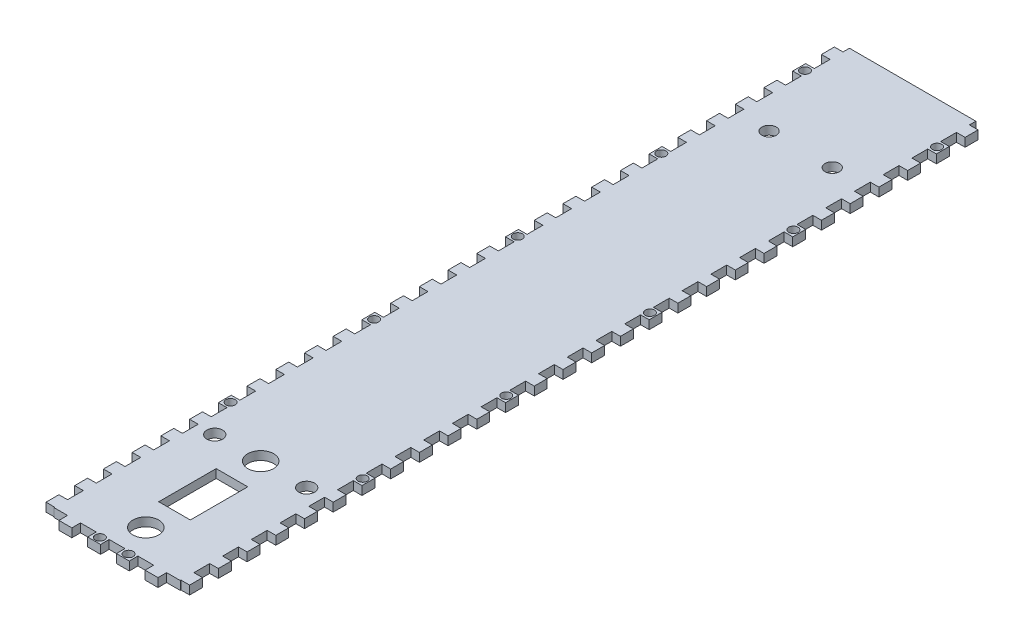
SolidWorks part; units mm, degrees
ref_plane "Plan de face" through (0, 0, 0) normal (0, 0, 1) x (1, 0, 0)
ref_plane "Plan de dessus" through (0, 0, 0) normal (0, 1, 0) x (1, 0, 0)
ref_plane "Plan de droite" through (0, 0, 0) normal (1, 0, 0) x (0, 0, -1)
sketch "Sketch1" plane through (0, 0, 0) normal (0, 0, 1) x (1, 0, 0)
  line L1 (-30.0201, 10.5217) -> (13.9799, 10.5217)
  line L2 (-30.0201, 10.5217) -> (-30.0201, 7.5217)
  line L3 (-30.0201, 7.5217) -> (13.9799, 7.5217)
  line L4 (13.9799, 10.5217) -> (13.9799, 7.5217)
  dimension "D1" = 44
  dimension "D2" = 3
extrude "Boss-Extrude1" add sketch "Sketch1" along normal blind 277
sketch "Sketch4" plane through (13.9799, 0, 0) normal (1, 0, 0) x (0, 0, -1)
  line L0 (-277, 10.5217) -> (0, 10.5217) construction
  line L1 (-276.75, 10.5217) -> (-272.25, 10.5217)
  line L2 (-276.75, 10.5217) -> (-276.75, 7.5217)
  line L3 (-276.75, 7.5217) -> (-272.25, 7.5217)
  line L4 (-272.25, 10.5217) -> (-272.25, 7.5217)
  line L5 (-277, 7.5217) -> (0, 7.5217) construction
  line L6 (-277, 7.5217) -> (-277, 10.5217) construction
  line L7 (-266.75, 10.5217) -> (-266.75, 7.5217)
  line L8 (-266.75, 10.5217) -> (-262.25, 10.5217)
  line L9 (-262.25, 10.5217) -> (-262.25, 7.5217)
  line L10 (-266.75, 7.5217) -> (-262.25, 7.5217)
  line L11 (-256.75, 10.5217) -> (-256.75, 7.5217)
  line L12 (-256.75, 10.5217) -> (-252.25, 10.5217)
  line L13 (-252.25, 10.5217) -> (-252.25, 7.5217)
  line L14 (-256.75, 7.5217) -> (-252.25, 7.5217)
  line L15 (-246.75, 10.5217) -> (-246.75, 7.5217)
  line L16 (-246.75, 10.5217) -> (-242.25, 10.5217)
  line L17 (-242.25, 10.5217) -> (-242.25, 7.5217)
  line L18 (-246.75, 7.5217) -> (-242.25, 7.5217)
  line L19 (-236.75, 10.5217) -> (-236.75, 7.5217)
  line L20 (-236.75, 10.5217) -> (-232.25, 10.5217)
  line L21 (-232.25, 10.5217) -> (-232.25, 7.5217)
  line L22 (-236.75, 7.5217) -> (-232.25, 7.5217)
  line L23 (-226.75, 10.5217) -> (-226.75, 7.5217)
  line L24 (-226.75, 10.5217) -> (-222.25, 10.5217)
  line L25 (-222.25, 10.5217) -> (-222.25, 7.5217)
  line L26 (-226.75, 7.5217) -> (-222.25, 7.5217)
  line L27 (-216.75, 10.5217) -> (-216.75, 7.5217)
  line L28 (-216.75, 10.5217) -> (-212.25, 10.5217)
  line L29 (-212.25, 10.5217) -> (-212.25, 7.5217)
  line L30 (-216.75, 7.5217) -> (-212.25, 7.5217)
  line L31 (-206.75, 10.5217) -> (-206.75, 7.5217)
  line L32 (-206.75, 10.5217) -> (-202.25, 10.5217)
  line L33 (-202.25, 10.5217) -> (-202.25, 7.5217)
  line L34 (-206.75, 7.5217) -> (-202.25, 7.5217)
  line L35 (-196.75, 10.5217) -> (-196.75, 7.5217)
  line L36 (-196.75, 10.5217) -> (-192.25, 10.5217)
  line L37 (-192.25, 10.5217) -> (-192.25, 7.5217)
  line L38 (-196.75, 7.5217) -> (-192.25, 7.5217)
  line L39 (-186.75, 10.5217) -> (-186.75, 7.5217)
  line L40 (-186.75, 10.5217) -> (-182.25, 10.5217)
  line L41 (-182.25, 10.5217) -> (-182.25, 7.5217)
  line L42 (-186.75, 7.5217) -> (-182.25, 7.5217)
  line L43 (-176.75, 10.5217) -> (-176.75, 7.5217)
  line L44 (-176.75, 10.5217) -> (-172.25, 10.5217)
  line L45 (-172.25, 10.5217) -> (-172.25, 7.5217)
  line L46 (-176.75, 7.5217) -> (-172.25, 7.5217)
  line L47 (-166.75, 10.5217) -> (-166.75, 7.5217)
  line L48 (-166.75, 10.5217) -> (-162.25, 10.5217)
  line L49 (-162.25, 10.5217) -> (-162.25, 7.5217)
  line L50 (-166.75, 7.5217) -> (-162.25, 7.5217)
  line L51 (-156.75, 10.5217) -> (-156.75, 7.5217)
  line L52 (-156.75, 10.5217) -> (-152.25, 10.5217)
  line L53 (-152.25, 10.5217) -> (-152.25, 7.5217)
  line L54 (-156.75, 7.5217) -> (-152.25, 7.5217)
  line L55 (-146.75, 10.5217) -> (-146.75, 7.5217)
  line L56 (-146.75, 10.5217) -> (-142.25, 10.5217)
  line L57 (-142.25, 10.5217) -> (-142.25, 7.5217)
  line L58 (-146.75, 7.5217) -> (-142.25, 7.5217)
  line L59 (-136.75, 10.5217) -> (-136.75, 7.5217)
  line L60 (-136.75, 10.5217) -> (-132.25, 10.5217)
  line L61 (-132.25, 10.5217) -> (-132.25, 7.5217)
  line L62 (-136.75, 7.5217) -> (-132.25, 7.5217)
  line L63 (-126.75, 10.5217) -> (-126.75, 7.5217)
  line L64 (-126.75, 10.5217) -> (-122.25, 10.5217)
  line L65 (-122.25, 10.5217) -> (-122.25, 7.5217)
  line L66 (-126.75, 7.5217) -> (-122.25, 7.5217)
  line L67 (-116.75, 10.5217) -> (-116.75, 7.5217)
  line L68 (-116.75, 10.5217) -> (-112.25, 10.5217)
  line L69 (-112.25, 10.5217) -> (-112.25, 7.5217)
  line L70 (-116.75, 7.5217) -> (-112.25, 7.5217)
  line L71 (-106.75, 10.5217) -> (-106.75, 7.5217)
  line L72 (-106.75, 10.5217) -> (-102.25, 10.5217)
  line L73 (-102.25, 10.5217) -> (-102.25, 7.5217)
  line L74 (-106.75, 7.5217) -> (-102.25, 7.5217)
  line L75 (-96.75, 10.5217) -> (-96.75, 7.5217)
  line L76 (-96.75, 10.5217) -> (-92.25, 10.5217)
  line L77 (-92.25, 10.5217) -> (-92.25, 7.5217)
  line L78 (-96.75, 7.5217) -> (-92.25, 7.5217)
  line L79 (-86.75, 10.5217) -> (-86.75, 7.5217)
  line L80 (-86.75, 10.5217) -> (-82.25, 10.5217)
  line L81 (-82.25, 10.5217) -> (-82.25, 7.5217)
  line L82 (-86.75, 7.5217) -> (-82.25, 7.5217)
  line L83 (-76.75, 10.5217) -> (-76.75, 7.5217)
  line L84 (-76.75, 10.5217) -> (-72.25, 10.5217)
  line L85 (-72.25, 10.5217) -> (-72.25, 7.5217)
  line L86 (-76.75, 7.5217) -> (-72.25, 7.5217)
  line L87 (-66.75, 10.5217) -> (-66.75, 7.5217)
  line L88 (-66.75, 10.5217) -> (-62.25, 10.5217)
  line L89 (-62.25, 10.5217) -> (-62.25, 7.5217)
  line L90 (-66.75, 7.5217) -> (-62.25, 7.5217)
  line L91 (-56.75, 10.5217) -> (-56.75, 7.5217)
  line L92 (-56.75, 10.5217) -> (-52.25, 10.5217)
  line L93 (-52.25, 10.5217) -> (-52.25, 7.5217)
  line L94 (-56.75, 7.5217) -> (-52.25, 7.5217)
  line L95 (-46.75, 10.5217) -> (-46.75, 7.5217)
  line L96 (-46.75, 10.5217) -> (-42.25, 10.5217)
  line L97 (-42.25, 10.5217) -> (-42.25, 7.5217)
  line L98 (-46.75, 7.5217) -> (-42.25, 7.5217)
  line L99 (-36.75, 10.5217) -> (-36.75, 7.5217)
  line L100 (-36.75, 10.5217) -> (-32.25, 10.5217)
  line L101 (-32.25, 10.5217) -> (-32.25, 7.5217)
  line L102 (-36.75, 7.5217) -> (-32.25, 7.5217)
  line L103 (-26.75, 10.5217) -> (-26.75, 7.5217)
  line L104 (-26.75, 10.5217) -> (-22.25, 10.5217)
  line L105 (-22.25, 10.5217) -> (-22.25, 7.5217)
  line L106 (-26.75, 7.5217) -> (-22.25, 7.5217)
  line L107 (-16.75, 10.5217) -> (-16.75, 7.5217)
  line L108 (-16.75, 10.5217) -> (-12.25, 10.5217)
  line L109 (-12.25, 10.5217) -> (-12.25, 7.5217)
  line L110 (-16.75, 7.5217) -> (-12.25, 7.5217)
  line L111 (-6.75, 10.5217) -> (-6.75, 7.5217)
  line L112 (-6.75, 10.5217) -> (-2.25, 10.5217)
  line L113 (-2.25, 10.5217) -> (-2.25, 7.5217)
  line L114 (-6.75, 7.5217) -> (-2.25, 7.5217)
  dimension "D1" = 0.25
  dimension "D2" = 4.5
  dimension "D3" = 28
extrude "Boss-Extrude2" add sketch "Sketch4" along normal blind 3
sketch "Sketch5" plane through (-30.0201, 0, 0) normal (-1, 0, 0) x (0, 0, 1)
  line L0 (277, 7.5217) -> (0, 7.5217) construction
  line L1 (276.75, 7.5217) -> (272.25, 7.5217)
  line L2 (276.75, 7.5217) -> (276.75, 10.5217)
  line L3 (276.75, 10.5217) -> (272.25, 10.5217)
  line L4 (272.25, 7.5217) -> (272.25, 10.5217)
  line L5 (277, 10.5217) -> (0, 10.5217) construction
  line L6 (277, 10.5217) -> (277, 7.5217) construction
  line L7 (266.75, 7.5217) -> (266.75, 10.5217)
  line L8 (266.75, 7.5217) -> (262.25, 7.5217)
  line L9 (262.25, 7.5217) -> (262.25, 10.5217)
  line L10 (266.75, 10.5217) -> (262.25, 10.5217)
  line L11 (256.75, 7.5217) -> (256.75, 10.5217)
  line L12 (256.75, 7.5217) -> (252.25, 7.5217)
  line L13 (252.25, 7.5217) -> (252.25, 10.5217)
  line L14 (256.75, 10.5217) -> (252.25, 10.5217)
  line L15 (246.75, 7.5217) -> (246.75, 10.5217)
  line L16 (246.75, 7.5217) -> (242.25, 7.5217)
  line L17 (242.25, 7.5217) -> (242.25, 10.5217)
  line L18 (246.75, 10.5217) -> (242.25, 10.5217)
  line L19 (236.75, 7.5217) -> (236.75, 10.5217)
  line L20 (236.75, 7.5217) -> (232.25, 7.5217)
  line L21 (232.25, 7.5217) -> (232.25, 10.5217)
  line L22 (236.75, 10.5217) -> (232.25, 10.5217)
  line L23 (226.75, 7.5217) -> (226.75, 10.5217)
  line L24 (226.75, 7.5217) -> (222.25, 7.5217)
  line L25 (222.25, 7.5217) -> (222.25, 10.5217)
  line L26 (226.75, 10.5217) -> (222.25, 10.5217)
  line L27 (216.75, 7.5217) -> (216.75, 10.5217)
  line L28 (216.75, 7.5217) -> (212.25, 7.5217)
  line L29 (212.25, 7.5217) -> (212.25, 10.5217)
  line L30 (216.75, 10.5217) -> (212.25, 10.5217)
  line L31 (206.75, 7.5217) -> (206.75, 10.5217)
  line L32 (206.75, 7.5217) -> (202.25, 7.5217)
  line L33 (202.25, 7.5217) -> (202.25, 10.5217)
  line L34 (206.75, 10.5217) -> (202.25, 10.5217)
  line L35 (196.75, 7.5217) -> (196.75, 10.5217)
  line L36 (196.75, 7.5217) -> (192.25, 7.5217)
  line L37 (192.25, 7.5217) -> (192.25, 10.5217)
  line L38 (196.75, 10.5217) -> (192.25, 10.5217)
  line L39 (186.75, 7.5217) -> (186.75, 10.5217)
  line L40 (186.75, 7.5217) -> (182.25, 7.5217)
  line L41 (182.25, 7.5217) -> (182.25, 10.5217)
  line L42 (186.75, 10.5217) -> (182.25, 10.5217)
  line L43 (176.75, 7.5217) -> (176.75, 10.5217)
  line L44 (176.75, 7.5217) -> (172.25, 7.5217)
  line L45 (172.25, 7.5217) -> (172.25, 10.5217)
  line L46 (176.75, 10.5217) -> (172.25, 10.5217)
  line L47 (166.75, 7.5217) -> (166.75, 10.5217)
  line L48 (166.75, 7.5217) -> (162.25, 7.5217)
  line L49 (162.25, 7.5217) -> (162.25, 10.5217)
  line L50 (166.75, 10.5217) -> (162.25, 10.5217)
  line L51 (156.75, 7.5217) -> (156.75, 10.5217)
  line L52 (156.75, 7.5217) -> (152.25, 7.5217)
  line L53 (152.25, 7.5217) -> (152.25, 10.5217)
  line L54 (156.75, 10.5217) -> (152.25, 10.5217)
  line L55 (146.75, 7.5217) -> (146.75, 10.5217)
  line L56 (146.75, 7.5217) -> (142.25, 7.5217)
  line L57 (142.25, 7.5217) -> (142.25, 10.5217)
  line L58 (146.75, 10.5217) -> (142.25, 10.5217)
  line L59 (136.75, 7.5217) -> (136.75, 10.5217)
  line L60 (136.75, 7.5217) -> (132.25, 7.5217)
  line L61 (132.25, 7.5217) -> (132.25, 10.5217)
  line L62 (136.75, 10.5217) -> (132.25, 10.5217)
  line L63 (126.75, 7.5217) -> (126.75, 10.5217)
  line L64 (126.75, 7.5217) -> (122.25, 7.5217)
  line L65 (122.25, 7.5217) -> (122.25, 10.5217)
  line L66 (126.75, 10.5217) -> (122.25, 10.5217)
  line L67 (116.75, 7.5217) -> (116.75, 10.5217)
  line L68 (116.75, 7.5217) -> (112.25, 7.5217)
  line L69 (112.25, 7.5217) -> (112.25, 10.5217)
  line L70 (116.75, 10.5217) -> (112.25, 10.5217)
  line L71 (106.75, 7.5217) -> (106.75, 10.5217)
  line L72 (106.75, 7.5217) -> (102.25, 7.5217)
  line L73 (102.25, 7.5217) -> (102.25, 10.5217)
  line L74 (106.75, 10.5217) -> (102.25, 10.5217)
  line L75 (96.75, 7.5217) -> (96.75, 10.5217)
  line L76 (96.75, 7.5217) -> (92.25, 7.5217)
  line L77 (92.25, 7.5217) -> (92.25, 10.5217)
  line L78 (96.75, 10.5217) -> (92.25, 10.5217)
  line L79 (86.75, 7.5217) -> (86.75, 10.5217)
  line L80 (86.75, 7.5217) -> (82.25, 7.5217)
  line L81 (82.25, 7.5217) -> (82.25, 10.5217)
  line L82 (86.75, 10.5217) -> (82.25, 10.5217)
  line L83 (76.75, 7.5217) -> (76.75, 10.5217)
  line L84 (76.75, 7.5217) -> (72.25, 7.5217)
  line L85 (72.25, 7.5217) -> (72.25, 10.5217)
  line L86 (76.75, 10.5217) -> (72.25, 10.5217)
  line L87 (66.75, 7.5217) -> (66.75, 10.5217)
  line L88 (66.75, 7.5217) -> (62.25, 7.5217)
  line L89 (62.25, 7.5217) -> (62.25, 10.5217)
  line L90 (66.75, 10.5217) -> (62.25, 10.5217)
  line L91 (56.75, 7.5217) -> (56.75, 10.5217)
  line L92 (56.75, 7.5217) -> (52.25, 7.5217)
  line L93 (52.25, 7.5217) -> (52.25, 10.5217)
  line L94 (56.75, 10.5217) -> (52.25, 10.5217)
  line L95 (46.75, 7.5217) -> (46.75, 10.5217)
  line L96 (46.75, 7.5217) -> (42.25, 7.5217)
  line L97 (42.25, 7.5217) -> (42.25, 10.5217)
  line L98 (46.75, 10.5217) -> (42.25, 10.5217)
  line L99 (36.75, 7.5217) -> (36.75, 10.5217)
  line L100 (36.75, 7.5217) -> (32.25, 7.5217)
  line L101 (32.25, 7.5217) -> (32.25, 10.5217)
  line L102 (36.75, 10.5217) -> (32.25, 10.5217)
  line L103 (26.75, 7.5217) -> (26.75, 10.5217)
  line L104 (26.75, 7.5217) -> (22.25, 7.5217)
  line L105 (22.25, 7.5217) -> (22.25, 10.5217)
  line L106 (26.75, 10.5217) -> (22.25, 10.5217)
  line L107 (16.75, 7.5217) -> (16.75, 10.5217)
  line L108 (16.75, 7.5217) -> (12.25, 7.5217)
  line L109 (12.25, 7.5217) -> (12.25, 10.5217)
  line L110 (16.75, 10.5217) -> (12.25, 10.5217)
  line L111 (6.75, 7.5217) -> (6.75, 10.5217)
  line L112 (6.75, 7.5217) -> (2.25, 7.5217)
  line L113 (2.25, 7.5217) -> (2.25, 10.5217)
  line L114 (6.75, 10.5217) -> (2.25, 10.5217)
  dimension "D1" = 0.25
  dimension "D2" = 4.5
  dimension "D3" = 28
extrude "Boss-Extrude3" add sketch "Sketch5" along normal blind 3
sketch "Sketch6" plane through (0, 0, 277) normal (0, 0, 1) x (1, 0, 0)
  line L0 (13.9799, 10.5217) -> (-30.0201, 10.5217) construction
  line L1 (-25.2701, 10.5217) -> (-20.7701, 10.5217)
  line L2 (-25.2701, 10.5217) -> (-25.2701, 7.5217)
  line L3 (-25.2701, 7.5217) -> (-20.7701, 7.5217)
  line L4 (-20.7701, 10.5217) -> (-20.7701, 7.5217)
  line L5 (-30.0201, 7.5217) -> (13.9799, 7.5217) construction
  line L6 (-30.0201, 7.5217) -> (-30.0201, 10.5217) construction
  line L7 (-15.2701, 10.5217) -> (-15.2701, 7.5217)
  line L8 (-15.2701, 10.5217) -> (-10.7701, 10.5217)
  line L9 (-10.7701, 10.5217) -> (-10.7701, 7.5217)
  line L10 (-15.2701, 7.5217) -> (-10.7701, 7.5217)
  line L11 (-5.2701, 10.5217) -> (-5.2701, 7.5217)
  line L12 (-5.2701, 10.5217) -> (-0.7701, 10.5217)
  line L13 (-0.7701, 10.5217) -> (-0.7701, 7.5217)
  line L14 (-5.2701, 7.5217) -> (-0.7701, 7.5217)
  line L15 (4.7299, 10.5217) -> (4.7299, 7.5217)
  line L16 (4.7299, 10.5217) -> (9.2299, 10.5217)
  line L17 (9.2299, 10.5217) -> (9.2299, 7.5217)
  line L18 (4.7299, 7.5217) -> (9.2299, 7.5217)
  dimension "D1" = 4.75
  dimension "D2" = 4.5
  dimension "D3" = 4
extrude "Boss-Extrude4" add sketch "Sketch6" along normal blind 3
sketch "Sketch7" plane through (0, 7.5217, 0) normal (0, -1, 0) x (1, 0, 0)
  line L0 (-8.0201, 277) -> (-8.0201, 0) construction
  line L1 (-10.7701, 277) -> (-5.2701, 277) construction
  line L2 (-30.0201, 0) -> (13.9799, 0) construction
  line L3 (13.9799, 276.75) -> (16.9799, 272.25) construction
  line L4 (16.9799, 266.75) -> (16.9799, 262.25) construction
  line L5 (16.9799, 276.75) -> (13.9799, 276.75) construction
  circle A0 centre (14.9799, 264.5) radius 1.6
  circle A1 centre (-31.0201, 264.5) radius 1.6
  circle A2 centre (-31.0201, 214.5) radius 1.6
  circle A3 centre (14.9799, 214.5) radius 1.6
  circle A4 centre (-31.0201, 164.5) radius 1.6
  circle A5 centre (14.9799, 164.5) radius 1.6
  circle A6 centre (-31.0201, 114.5) radius 1.6
  circle A7 centre (14.9799, 114.5) radius 1.6
  circle A8 centre (-31.0201, 64.5) radius 1.6
  circle A9 centre (14.9799, 64.5) radius 1.6
  circle A10 centre (-31.0201, 14.5) radius 1.6
  circle A11 centre (14.9799, 14.5) radius 1.6
  point P14 (0, 0)
  dimension "D1" = 6
  dimension "D3" = 3.2
  dimension "D4" = 2
  dimension "D2" = 12.25
extrude "Cut-Extrude1" cut sketch "Sketch7" against normal blind 3
sketch "Sketch8" plane through (0, 7.5217, 0) normal (0, -1, 0) x (1, 0, 0)
  line L0 (-8.0201, 0) -> (-8.0201, 54.5316) construction
  line L1 (-30.0201, 0) -> (13.9799, 0) construction
  circle A0 centre (-19.0201, 39) radius 2.5
  circle A1 centre (2.9799, 39) radius 2.5
  dimension "D1" = 5
  dimension "D2" = 11
  dimension "D3" = 39
extrude "Cut-Extrude2" cut sketch "Sketch8" against normal blind 12
sketch "Sketch9" plane through (0, 7.5217, 0) normal (0, -1, 0) x (-1, 0, 0)
  line L1 (0.7701, -280) -> (5.2701, -280) construction
  line L2 (10.7701, -280) -> (15.2701, -280) construction
  circle A0 centre (13.0201, -278) radius 1.6
  circle A1 centre (3.0201, -278) radius 1.6
  point P0 (0, 0)
  dimension "D1" = 3.2
  dimension "D2" = 3.2
  dimension "D3" = 2
  dimension "D4" = 2
extrude "Cut-Extrude3" cut sketch "Sketch9" against normal blind 12
sketch "Sketch11" plane through (0, 7.5217, 0) normal (0, -1, 0) x (1, 0, 0)
  line L0 (-10.7701, 277) -> (-5.2701, 277) construction
  line L2 (-13.5201, 257) -> (-2.5201, 257)
  line L3 (-13.5201, 257) -> (-13.5201, 237)
  line L4 (-13.5201, 237) -> (-2.5201, 237)
  line L5 (-2.5201, 257) -> (-2.5201, 237)
  circle A0 centre (-8.0201, 267) radius 4.5
  circle A1 centre (-8.0201, 227) radius 4.5
  circle A2 centre (-24.0201, 227) radius 2.75
  circle A3 centre (7.9799, 227) radius 2.75
  point P8 (-8.0201, 277)
  point P11 (-8.0201, 257)
  dimension "D1" = 9
  dimension "D2" = 9
  dimension "D8" = 5.5
  dimension "D9" = 5.5
  dimension "D3" = 40
  dimension "D4" = 10
  dimension "D5" = 11
  dimension "D6" = 10
  dimension "D7" = 10
  dimension "D10" = 32
  dimension "D11" = 16
extrude "Cut-Extrude4" cut sketch "Sketch11" against normal through all
extrude "Boss-Extrude5" add sketch "Sketch7<2>" against normal through all separate body contours A0 | A1 region at (14.9799, 7.5217, 264.5) region at (-31.0201, 7.5217, 264.5)
sketch "Sketch7<2>" plane through (0, 7.5217, 0) normal (0, -1, 0) x (1, 0, 0) same geometry as "Sketch7"
combine bodies "Combine1" operation type add bodies to combine 109 113 112
